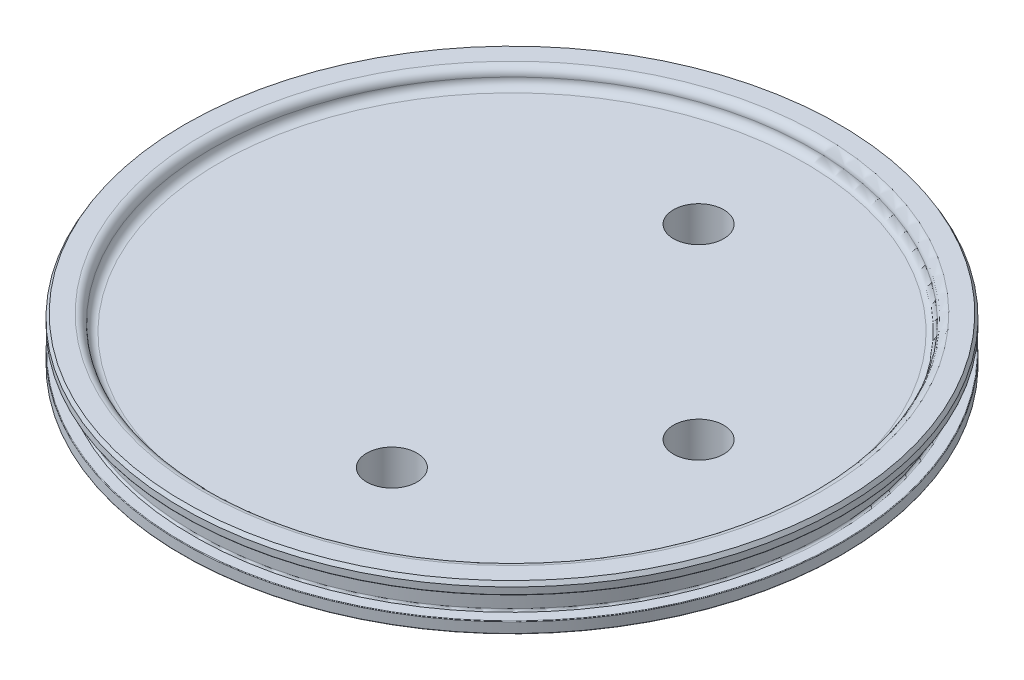
SolidWorks part; units mm, degrees
material "6061-T6 (SS)"
ref_plane "Front Plane" through (0, 0, 0) normal (0, 0, 1) x (1, 0, 0)
ref_plane "Top Plane" through (0, 0, 0) normal (0, 1, 0) x (1, 0, 0)
ref_plane "Right Plane" through (0, 0, 0) normal (1, 0, 0) x (0, 0, -1)
sketch "Sketch1" plane through (0, 0, 0) normal (0, 0, 1) x (1, 0, 0)
  line L0 (0, 48.1922) -> (0, -25.6743) construction
  line L1 (0, 0) -> (72.898, 0)
  line L2 (72.898, 0) -> (72.898, 2.4638)
  line L3 (72.898, 2.4638) -> (70.0532, 2.4638)
  line L4 (70.0532, 2.4638) -> (70.0532, 7.4422)
  line L5 (70.0532, 7.4422) -> (72.898, 7.4422)
  line L6 (72.898, 7.4422) -> (72.898, 9.906)
  line L7 (72.898, 9.906) -> (66.548, 9.906)
  line L8 (66.548, 9.906) -> (66.548, 6.35)
  line L9 (66.548, 6.35) -> (0, 6.35)
  line L10 (0, 6.35) -> (0, 0)
  dimension "D1" = 145.796
  dimension "D2" = 4.9784
  dimension "D3" = 2.8448
  dimension "D4" = 9.906
  dimension "D5" = 6.35
  dimension "D6" = 6.35
revolve "Revolve1" add sketch "Sketch1" angle 360 about L0
sketch "Sketch6" plane through (0, 0, 0) normal (0, -1, 0) x (1, 0, 0)
  circle A0 centre (0, 0) radius 66.04
  dimension "D1" = 132.08
extrude "Boss-Extrude1" add sketch "Sketch6" along normal blind 2.54
hole_wizard "Pipe Tap Drill for 1/4 Tap - GN2" positions "Sketch2" profile "Sketch3" hole size "1/4" standard "ANSI Inch" end condition through all
sketch "Sketch2" plane through (0, 6.35, 0) normal (0, 1, 0) x (1, 0, 0)
  line L3 (0, 41.275) -> (0, 0) construction
  line L4 (0, 0) -> (41.275, 0) construction
  line L6 (0, 0) -> (12.7, -39.2726) construction
  point P41 (12.7, -39.2726)
  point P44 (0, 41.275)
  point P47 (41.275, 0)
  dimension "D1" = 41.275
  dimension "D2" = 41.275
  dimension "D3" = 41.275
  dimension "D4" = 12.7
sketch "Sketch3" plane through (12.7, 6.35, 39.2726) normal (1, 0, 0) x (0, 0, 1)
  line L0 (0, 0) -> (0, 8.89)
  line L1 (0, 8.89) -> (5.5626, 8.89)
  line L2 (5.5626, 8.89) -> (5.5626, 0)
  line L5 (5.5626, 0) -> (0, 0)
  line L11 (0, -6.35) -> (0, 107.95) construction
  dimension "Thru Hole Dia." = 11.1252
  dimension "Thru Hole Depth" = 8.89
fillet "CNC ID Fillet" radius 0.4064 3 edges at (-70.0532, 7.4422, 0) (-70.0532, 2.4638, 0) (66.04, 0, 0)
fillet "CNC OD Fillet" radius 0.127 4 edges at (-72.898, 7.4422, 0) (-72.898, 2.4638, 0) (66.04, -2.54, 0) (-72.898, 0, 0)
chamfer "CNC Chamfers" distance 0.508 angle 60 1 edges at (-72.898, 9.906, 0) first distance on face at (-66.548, 9.906, 0)
fillet "CNC Bore Fillet" radius 1.778 2 edges at (-66.548, 6.35, 0) (-66.548, 9.906, 0)
